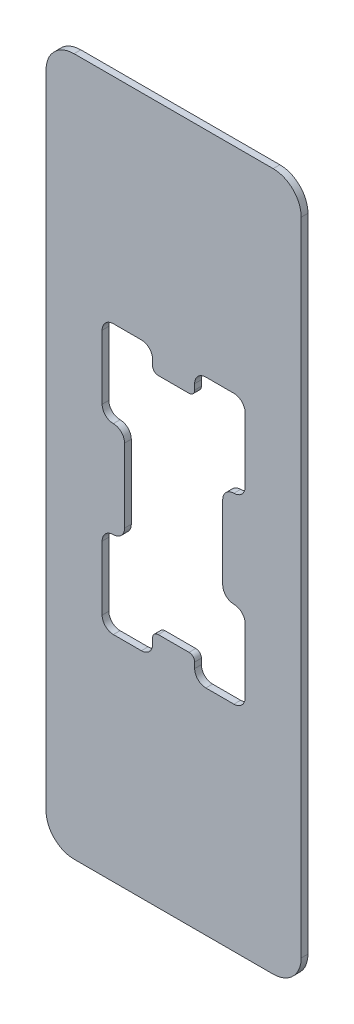
SolidWorks part; units mm, degrees
ref_plane "Front Plane" through (0, 0, 0) normal (0, 0, 1) x (1, 0, 0)
ref_plane "Top Plane" through (0, 0, 0) normal (0, 1, 0) x (1, 0, 0)
ref_plane "Right Plane" through (0, 0, 0) normal (1, 0, 0) x (0, 0, -1)
sketch "Sketch1" plane through (0, 0, 0) normal (0, 0, 1) x (1, 0, 0)
  line L1 (0, 0) -> (45.5, 0)
  line L2 (0, 0) -> (0, 124.4)
  line L3 (0, 124.4) -> (45.5, 124.4)
  line L4 (45.5, 0) -> (45.5, 124.4)
  dimension "D1" = 45.5
  dimension "D2" = 124.4
extrude "Boss-Extrude1" add sketch "Sketch1" along normal blind 1.2
sketch "Sketch2" plane through (0, 0, 1.2) normal (0, 0, 1) x (1, 0, 0)
  line L0 (22.75, 124.4) -> (22.75, 0) construction
  line L1 (45.5, 124.4) -> (0, 124.4) construction
  line L2 (0, 0) -> (45.5, 0) construction
  line L3 (0, 62.2) -> (45.5, 62.2) construction
  line L4 (0, 124.4) -> (0, 0) construction
  line L5 (45.5, 0) -> (45.5, 124.4) construction
  line L6 (35.5, 86.2) -> (26.5, 86.2)
  line L7 (14, 82.2) -> (31.5, 82.2)
  line L8 (14, 82.2) -> (14, 42.2)
  line L9 (14, 42.2) -> (31.5, 42.2)
  line L10 (31.5, 82.2) -> (31.5, 42.2)
  line L11 (14, 82.2) -> (31.5, 42.2) construction
  line L12 (14, 42.2) -> (31.5, 82.2) construction
  line L13 (10, 86.2) -> (19, 86.2)
  line L14 (10, 86.2) -> (10, 70.7714)
  line L15 (10, 70.7714) -> (19, 70.7714)
  line L16 (19, 86.2) -> (19, 70.7714)
  line L17 (35.5, 86.2) -> (35.5, 70.7714)
  line L18 (35.5, 70.7714) -> (26.5, 70.7714)
  line L19 (26.5, 86.2) -> (26.5, 70.7714)
  line L20 (26.5, 38.2) -> (26.5, 53.6286)
  line L21 (35.5, 53.6286) -> (26.5, 53.6286)
  line L22 (35.5, 38.2) -> (35.5, 53.6286)
  line L23 (35.5, 38.2) -> (26.5, 38.2)
  line L24 (10, 38.2) -> (19, 38.2)
  line L25 (10, 38.2) -> (10, 53.6286)
  line L26 (10, 53.6286) -> (19, 53.6286)
  line L27 (19, 38.2) -> (19, 53.6286)
  point P12 (22.75, 62.2)
  dimension "D1" = 17.5
  dimension "D2" = 40
  dimension "D3" = 4
  dimension "D4" = 4
  dimension "D5" = 5
extrude "Cut-Extrude1" cut sketch "Sketch2" against normal blind 1.6 contours L16 L13 L14 L15 L8 L7 | L16 L7 L8 L15 | L27 L9 L20 L21 L10 L18 L19 L7 L16 L15 L8 L26 | L7 L19 L18 L10 | L6 L19 L7 L10 L18 L17 | L23 L22 L21 L10 L9 L20 | L10 L21 L20 L9 | L24 L27 L9 L8 L26 L25 | L9 L27 L26 L8 region at (32.3986, 79.8843, 1.2) region at (22.75, 62.2, 1.2) region at (29, 76.4857, 1.2) region at (16.5, 76.4857, 1.2) region at (13.1014, 79.8843, 1.2) region at (32.3986, 44.5157, 1.2) region at (29, 47.9143, 1.2) region at (16.5, 47.9143, 1.2) region at (13.1014, 44.5157, 1.2)
fillet "Fillet1" radius 2 16 edges at (10, 70.7714, 0.6) (19, 86.2, 0.6) (26.5, 86.2, 0.6) (35.5, 86.2, 0.6) (35.5, 70.7714, 0.6) (31.5, 70.7714, 0.6) (31.5, 53.6286, 0.6) (35.5, 53.6286, 0.6) (35.5, 38.2, 0.6) (26.5, 38.2, 0.6) (19, 38.2, 0.6) (10, 38.2, 0.6) (10, 53.6286, 0.6) (14, 53.6286, 0.6) (14, 70.7714, 0.6) (10, 86.2, 0.6)
fillet "Fillet2" radius 1 4 edges at (26.5, 42.2, 0.6) (19, 42.2, 0.6) (19, 82.2, 0.6) (26.5, 82.2, 0.6)
fillet "Fillet3" radius 5 4 edges at (0, 0, 0.6) (45.5, 0, 0.6) (45.5, 124.4, 0.6) (0, 124.4, 0.6)
